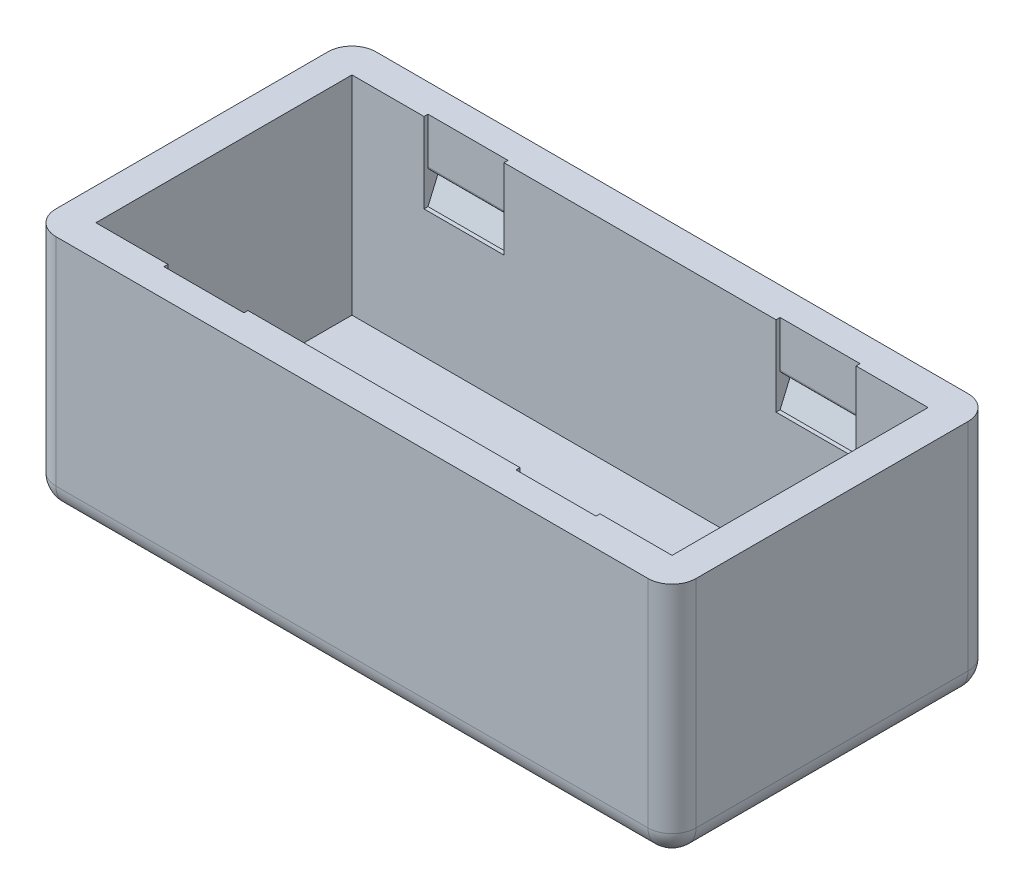
SolidWorks part; units mm, degrees
ref_plane "Front Plane" through (0, 0, 0) normal (0, 0, 1) x (1, 0, 0)
ref_plane "Top Plane" through (0, 0, 0) normal (0, 1, 0) x (1, 0, 0)
ref_plane "Right Plane" through (0, 0, 0) normal (1, 0, 0) x (0, 0, -1)
sketch "Sketch1" plane through (0, 0, 0) normal (0, 1, 0) x (1, 0, 0)
  line L1 (-20, 10) -> (20, 10)
  line L2 (-20, 10) -> (-20, -10)
  line L3 (-20, -10) -> (20, -10)
  line L4 (20, 10) -> (20, -10)
  line L5 (-20, 10) -> (20, -10) construction
  line L6 (-20, -10) -> (20, 10) construction
  point P0 (0, 0)
  dimension "D1" = 40
  dimension "D2" = 20
extrude "Boss-Extrude1" add sketch "Sketch1" along normal blind 15
shell "Shell2" thickness 2 removed face at (0, 15, 0)
sketch "Sketch2" plane through (0, 0, 0) normal (1, 0, 0) x (0, 0, -1)
  line L0 (8.25, 15) -> (8.25, 12.1442)
  line L1 (-10, 15) -> (10, 15) construction
  line L2 (8.3868, 11.9544) -> (9, 11.75)
  line L3 (9, 11.75) -> (8.25, 10)
  line L4 (8.25, 10) -> (7.25, 10)
  line L6 (7.25, 10) -> (7.25, 15)
  line L7 (7.25, 15) -> (8.25, 15)
  line L8 (8.25, 12) -> (8.25, 10) construction
  line L9 (10, 15) -> (10, 0) construction
  line L10 (8, 15) -> (8, 10)
  arc A0 (8.25, 12.1442) -> (8.3868, 11.9544) centre (8.45, 12.1442) ccw
  dimension "D7" = 0.2
  dimension "D1" = 3
  dimension "D2" = 5
  dimension "D3" = 1
  dimension "D4" = 1
  dimension "D5" = 0.25
  dimension "D6" = 1.75
extrude "Cut-Extrude1" cut sketch "Sketch2" against normal mid plane 5 from offset 11 contours L2 L8 L3 | L8 L0 L7 L10 L4 region at (0, 12.0312, -8.2657) offset against normal yes
mirror "Mirror1" about plane through (0, 0, 0) normal (1, 0, 0) of "Cut-Extrude1"
mirror "Mirror2" about plane through (0, 0, 0) normal (0, 0, 1) of "Mirror1"
fillet "Fillet1" radius 1.5 8 edges at (0, 0, -10) (-20, 0, 0) (0, 0, 10) (20, 0, 0) (-20, 7.5, -10) (20, 7.5, -10) (20, 7.5, 10) (-20, 7.5, 10)
